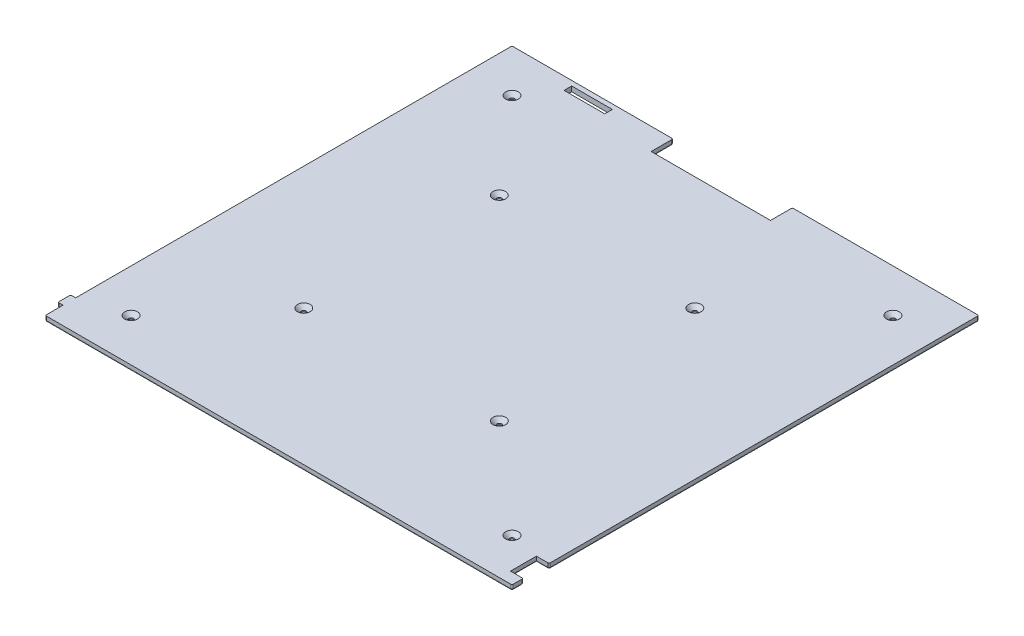
SolidWorks part; units mm, degrees
ref_plane "Front Plane" through (0, 0, 0) normal (0, 0, 1) x (1, 0, 0)
ref_plane "Top Plane" through (0, 0, 0) normal (0, 1, 0) x (1, 0, 0)
ref_plane "Right Plane" through (0, 0, 0) normal (1, 0, 0) x (0, 0, -1)
sketch "Sketch1" plane through (0, 0, 0) normal (0, 1, 0) x (1, 0, 0)
  line L0 (-92, 85.9) -> (-92, -85.9) construction
  line L1 (-28.4, 85.9) -> (-92, 85.9) construction
  line L2 (-28.4, 77.3) -> (-28.4, 85.9) construction
  line L3 (18.4, 77.3) -> (-28.4, 77.3) construction
  line L4 (18.4, 85.9) -> (18.4, 77.3) construction
  line L5 (92, 85.9) -> (18.4, 85.9) construction
  line L6 (92, -83.5) -> (92, 85.9) construction
  line L7 (87, -83.5) -> (92, -83.5) construction
  line L8 (87, -93.5) -> (87, -83.5) construction
  line L9 (92, -93.5) -> (87, -93.5) construction
  line L10 (92, -98.1) -> (92, -93.5) construction
  line L11 (-92, -98.1) -> (92, -98.1) construction
  line L12 (-92, -91.1) -> (-92, -98.1) construction
  line L13 (-94, -91.1) -> (-92, -91.1) construction
  line L14 (-94, -85.9) -> (-94, -91.1) construction
  line L15 (-92, -85.9) -> (-94, -85.9) construction
  line L16 (-91.9, 85.8) -> (-91.9, -86)
  line L17 (-91.9, -86) -> (-93.9, -86)
  line L18 (-93.9, -86) -> (-93.9, -91)
  line L19 (-93.9, -91) -> (-91.9, -91)
  line L20 (-91.9, -91) -> (-91.9, -98)
  line L21 (-91.9, -98) -> (91.9, -98)
  line L22 (91.9, -98) -> (91.9, -93.6)
  line L23 (91.9, -93.6) -> (86.9, -93.6)
  line L24 (86.9, -93.6) -> (86.9, -83.4)
  line L25 (86.9, -83.4) -> (91.9, -83.4)
  line L26 (91.9, -83.4) -> (91.9, 85.8)
  line L27 (91.9, 85.8) -> (18.5, 85.8)
  line L28 (18.5, 85.8) -> (18.5, 77.2)
  line L29 (18.5, 77.2) -> (-28.5, 77.2)
  line L30 (-28.5, 77.2) -> (-28.5, 85.8)
  line L31 (-28.5, 85.8) -> (-91.9, 85.8)
  point P16 (0, -98.1)
  point P18 (-92, 0)
  dimension "D1" = 169.4
  dimension "D2" = 171.8
  dimension "D3" = 63.6
  dimension "D4" = 73.6
  dimension "D5" = 46.8
  dimension "D6" = 8.6
  dimension "D7" = 10
  dimension "D8" = 5
  dimension "D9" = 5.2
  dimension "D10" = 7
  dimension "D11" = 2
  dimension "D12" = 0.1
extrude "Boss-Extrude1" add sketch "Sketch1" along normal blind 2
sketch "Sketch2" plane through (0, 0, 0) normal (0, -1, 0) x (1, 0, 0)
  circle A0 centre (75, -68.9) radius 1
  circle A1 centre (-75, -68.9) radius 1
  circle A2 centre (-75, 81.1) radius 1
  circle A3 centre (75, 81.1) radius 1
  circle A4 centre (33.5, -32.4) radius 1
  circle A5 centre (-43.5, -32.4) radius 1
  circle A6 centre (-43.5, 44.6) radius 1
  circle A7 centre (33.5, 44.6) radius 1
  dimension "D1" = 2
  dimension "D2" = 2
  dimension "D3" = 2
  dimension "D4" = 2
  dimension "D5" = 2
  dimension "D6" = 2
  dimension "D7" = 2
  dimension "D8" = 2
extrude "Cut-Extrude1" cut sketch "Sketch2" against normal through all
chamfer "Chamfer1" distance 1.5 distance2 1.5 1 edges at (-75, 2, -69.9)
chamfer "Chamfer2" distance 1.5 angle 45 7 edges at (75, 2, 80.1) (33.5, 2, 43.6) (75, 2, -69.9) (33.5, 2, -33.4) (-43.5, 2, -33.4) (-43.5, 2, 43.6) (-75, 2, 80.1)
fillet "Fillet1" radius 0.5 16 edges at (-91.9, 0, 0.1) (-92.9, 0, 86) (-93.9, 0, 88.5) (-92.9, 0, 91) (-91.9, 0, 94.5) (0, 0, 98) (91.9, 0, 95.8) (89.4, 0, 93.6) (86.9, 0, 88.5) (89.4, 0, 83.4) (91.9, 0, -1.2) (55.2, 0, -85.8) (18.5, 0, -81.5) (-5, 0, -77.2) (-28.5, 0, -81.5) (-60.2, 0, -85.8)
fillet "Fillet2" radius 0.5 20 edges at (-91.7536, 0.1464, -85.6536) (-28.6464, 0.1464, -85.6536) (18.6464, 0.1464, -85.6536) (91.7536, 0.1464, -85.6536) (91.7536, 0.1464, 83.2536) (91.7536, 0.1464, 93.7464) (91.7536, 0.1464, 97.8536) (-93.7536, 0.1464, 86.1464) (-93.7536, 0.1464, 90.8536) (-91.7536, 0.1464, 97.8536) (-91.9, 1.25, -85.8) (-28.5, 1.25, -85.8) (18.5, 1.25, -85.8) (91.9, 1.25, -85.8) (91.9, 1.25, 83.4) (91.9, 1.25, 93.6) (91.9, 1.25, 98) (-93.9, 1.25, 86) (-93.9, 1.25, 91) (-91.9, 1.25, 98)
sketch "Sketch3" plane through (0, 0, 0) normal (0, -1, 0) x (1, 0, 0)
  line L1 (-50.5, -83.9) -> (-66.5, -83.9)
  line L2 (-50.5, -83.9) -> (-50.5, -80.9)
  line L3 (-50.5, -80.9) -> (-66.5, -80.9)
  line L4 (-66.5, -83.9) -> (-66.5, -80.9)
extrude "Cut-Extrude2" cut sketch "Sketch3" against normal through all
